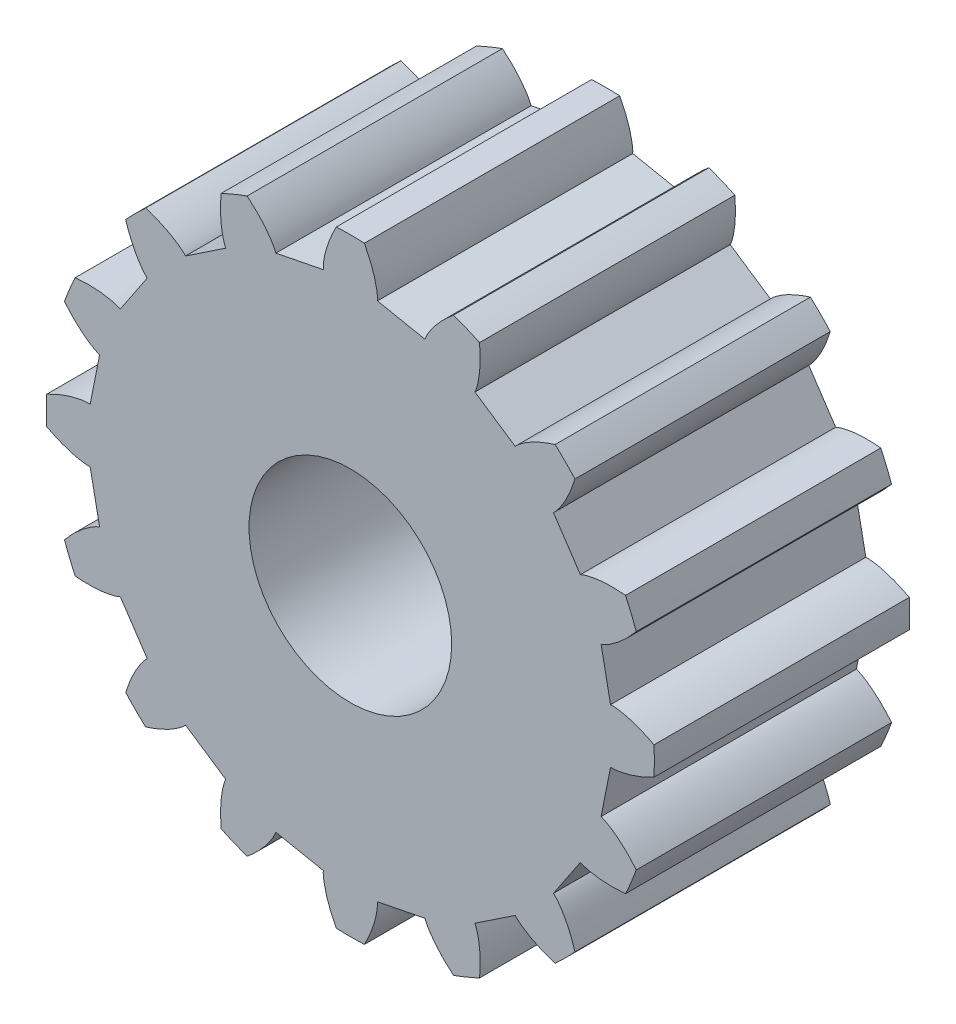
SolidWorks part; units mm, degrees
material "Plain Carbon Steel"
ref_plane "Front Plane" through (0, 0, 0) normal (0, 0, 1) x (1, 0, 0)
ref_plane "Top Plane" through (0, 0, 0) normal (0, 1, 0) x (1, 0, 0)
ref_plane "Right Plane" through (0, 0, 0) normal (1, 0, 0) x (0, 0, -1)
sketch "Sketch1" plane through (0, 0, 0) normal (0, 0, 1) x (1, 0, 0)
  circle A0 centre (0, 0) radius 14.2875
  dimension "D1" = 28.575
extrude "Boss-Extrude1" add sketch "Sketch1" along normal blind 12
sketch "Sketch2" plane through (0, 0, 0) normal (0, 0, 1) x (1, 0, 0)
  spline S0 degree 4 poles (12.2294, 1.273) (12.2326, 1.2733) (12.2415, 1.274) (12.2584, 1.2748) (12.286, 1.2754) (12.3212, 1.2753) (12.3668, 1.2738) (12.4205, 1.2707) (12.4797, 1.2656) (12.5441, 1.2584) (12.6083, 1.2497) (12.6724, 1.2397) (12.7362, 1.2284) (12.8134, 1.2132) (12.906, 1.193) (13.014, 1.1663) (13.1364, 1.1326) (13.2609, 1.0943) (13.3831, 1.0536) (13.5062, 1.0089) (13.6252, 0.9632) (13.7483, 0.912) (13.8617, 0.8629) (13.9883, 0.8039) (14.0903, 0.7551) (14.2242, 0.6865) (14.3032, 0.6448) (14.3953, 0.5944) (14.4361, 0.5713) (14.4612, 0.5571) knots 0 0 0 0 0 0.005377 0.015084 0.028532 0.04661 0.064855 0.092111 0.119476 0.146842 0.174209 0.201575 0.228941 0.256307 0.307035 0.361767 0.4165 0.471232 0.525964 0.580697 0.635429 0.690161 0.744894 0.799626 0.854358 0.909091 0.954545 1 1 1 1 1 construction
  spline S1 degree 4 poles (12.2294, 1.273) (12.2326, 1.2733) (12.2415, 1.274) (12.2584, 1.2748) (12.286, 1.2754) (12.3212, 1.2753) (12.3668, 1.2738) (12.4205, 1.2707) (12.4797, 1.2656) (12.5441, 1.2584) (12.6083, 1.2497) (12.6724, 1.2397) (12.7362, 1.2284) (12.8134, 1.2132) (12.906, 1.193) (13.014, 1.1663) (13.1364, 1.1326) (13.2609, 1.0943) (13.3831, 1.0536) (13.5062, 1.0089) (13.6252, 0.9632) (13.7483, 0.912) (13.8617, 0.8629) (13.9883, 0.8039) (14.0903, 0.7551) (14.1952, 0.7014) (14.2462, 0.6748) (14.2722, 0.661) knots 0 0 0 0 0 0.005377 0.015084 0.028532 0.04661 0.064855 0.092111 0.119476 0.146842 0.174209 0.201575 0.228941 0.256307 0.307035 0.361767 0.4165 0.471232 0.525964 0.580697 0.635429 0.690161 0.744894 0.799626 0.854358 0.909091 0.909091 0.909091 0.909091 0.909091
  spline S2 degree 4 poles (11.7856, 3.5039) (11.7887, 3.5048) (11.7972, 3.5076) (11.8131, 3.5133) (11.8388, 3.5233) (11.8713, 3.5369) (11.9129, 3.5557) (11.9614, 3.5792) (12.0141, 3.6065) (12.0708, 3.6378) (12.1268, 3.6704) (12.1821, 3.7042) (12.2368, 3.739) (12.3023, 3.7826) (12.3801, 3.8367) (12.4697, 3.9027) (12.5699, 3.9807) (12.6702, 4.0637) (12.7676, 4.1481) (12.8642, 4.2365) (12.9566, 4.3243) (13.0508, 4.4187) (13.1368, 4.5074) (13.2311, 4.6104) (13.3067, 4.6945) (13.4042, 4.8091) (13.4611, 4.8779) (13.527, 4.9597) (13.5558, 4.9967) (13.5736, 5.0194) knots 0 0 0 0 0 0.005377 0.015084 0.028532 0.04661 0.064855 0.092111 0.119476 0.146842 0.174209 0.201575 0.228941 0.256307 0.307035 0.361767 0.4165 0.471232 0.525964 0.580697 0.635429 0.690161 0.744894 0.799626 0.854358 0.909091 0.954545 1 1 1 1 1 construction
  spline S3 degree 4 poles (11.7856, 3.5039) (11.7887, 3.5048) (11.7972, 3.5076) (11.8131, 3.5133) (11.8388, 3.5233) (11.8713, 3.5369) (11.9129, 3.5557) (11.9614, 3.5792) (12.0141, 3.6065) (12.0708, 3.6378) (12.1268, 3.6704) (12.1821, 3.7042) (12.2368, 3.739) (12.3023, 3.7826) (12.3801, 3.8367) (12.4697, 3.9027) (12.5699, 3.9807) (12.6702, 4.0637) (12.7676, 4.1481) (12.8642, 4.2365) (12.9566, 4.3243) (13.0508, 4.4187) (13.1368, 4.5074) (13.2311, 4.6104) (13.3067, 4.6945) (13.3831, 4.7842) (13.42, 4.8284) (13.4387, 4.8511) knots 0 0 0 0 0 0.005377 0.015084 0.028532 0.04661 0.064855 0.092111 0.119476 0.146842 0.174209 0.201575 0.228941 0.256307 0.307035 0.361767 0.4165 0.471232 0.525964 0.580697 0.635429 0.690161 0.744894 0.799626 0.854358 0.909091 0.909091 0.909091 0.909091 0.909091
  spline S4 degree 1 poles (11.7856, 3.5039) (12.2294, 1.273) knots 0 0 1 1 construction
  spline S5 degree 1 poles (11.7856, 3.5039) (12.2294, 1.273) knots 0 0 1 1
  spline S6 degree 1 poles (14.2722, 0.661) (59.9358, 2.7757) knots 0 0 1 1 construction
  spline S7 degree 1 poles (14.2722, 0.661) (59.9358, 2.7757) knots 0 0 1 1
  spline S8 degree 4 poles (59.9924, 0.9679) (59.9914, 1.0088) (59.9898, 1.0795) (59.9907, 1.1275) (59.9804, 1.476) (59.9801, 1.6756) (59.9479, 2.5069) (59.9368, 2.7775) (59.9022, 3.4404) (59.8776, 3.8389) (59.8408, 4.3845) (59.7915, 5.0197) (59.7245, 5.7708) (59.636, 6.6216) (59.5352, 7.4745) (59.4224, 8.3239) (59.2973, 9.1728) (59.1602, 10.019) (59.0109, 10.8638) (58.8497, 11.7057) (58.6762, 12.5461) (58.4912, 13.3827) (58.2935, 14.2185) (58.085, 15.0482) (57.8629, 15.88) (57.632, 16.7001) (57.3841, 17.531) (57.1335, 18.3336) (56.8891, 19.0737) (56.6979, 19.635) (56.4391, 20.3656) (56.342, 20.6304) (56.0571, 21.4012) (55.9787, 21.592) (55.8562, 21.9145) (55.8362, 21.9603) (55.8108, 22.0259) (55.7963, 22.0637) knots 0 0 0 0 0 0.00524 0.010479 0.020959 0.041918 0.083333 0.103175 0.123016 0.142857 0.162698 0.202381 0.242063 0.281746 0.321429 0.361111 0.400794 0.440476 0.480159 0.519841 0.559524 0.599206 0.638889 0.678571 0.718254 0.757937 0.797619 0.837302 0.876984 0.896825 0.916667 0.958082 0.979041 0.989521 0.99476 1 1 1 1 1 construction
  spline S9 degree 4 poles (59.9358, 2.7757) (59.9316, 2.8649) (59.9226, 3.0495) (59.9022, 3.4404) (59.8776, 3.8389) (59.8408, 4.3845) (59.7915, 5.0197) (59.7245, 5.7708) (59.636, 6.6216) (59.5352, 7.4745) (59.4224, 8.3239) (59.2973, 9.1728) (59.1602, 10.019) (59.0109, 10.8638) (58.8497, 11.7057) (58.6762, 12.5461) (58.4912, 13.3827) (58.2935, 14.2185) (58.085, 15.0482) (57.8629, 15.88) (57.632, 16.7001) (57.3841, 17.531) (57.1335, 18.3336) (56.8891, 19.0737) (56.6979, 19.635) (56.5279, 20.115) (56.466, 20.288) (56.4356, 20.372) knots 0.083333 0.083333 0.083333 0.083333 0.083333 0.103175 0.123016 0.142857 0.162698 0.202381 0.242063 0.281746 0.321429 0.361111 0.400794 0.440476 0.480159 0.519841 0.559524 0.599206 0.638889 0.678571 0.718254 0.757937 0.797619 0.837302 0.876984 0.896825 0.916667 0.916667 0.916667 0.916667 0.916667
  spline S10 degree 1 poles (56.4356, 20.372) (13.4387, 4.8511) knots 0 0 1 1 construction
  spline S11 degree 1 poles (56.4356, 20.372) (13.4387, 4.8511) knots 0 0 1 1
extrude "Cut-Extrude2" cut sketch "Sketch2" against normal blind 13 and the other way blind 13
ref_axis "Axis1" through (0, 0, -0.6) along (0, 0, 1)
pattern_circular "CirPattern1" count 16 over 360 about axis through (0, 0, -0.6) along (0, 0, 1) of "Cut-Extrude2"
sketch "Sketch3" plane through (0, 0, 0) normal (0, 0, 1) x (1, 0, 0)
  circle A0 centre (0, 0) radius 4.7625
  dimension "D1" = 9.525
extrude "Cut-Extrude4" cut sketch "Sketch3" against normal blind 14 and the other way blind 14
